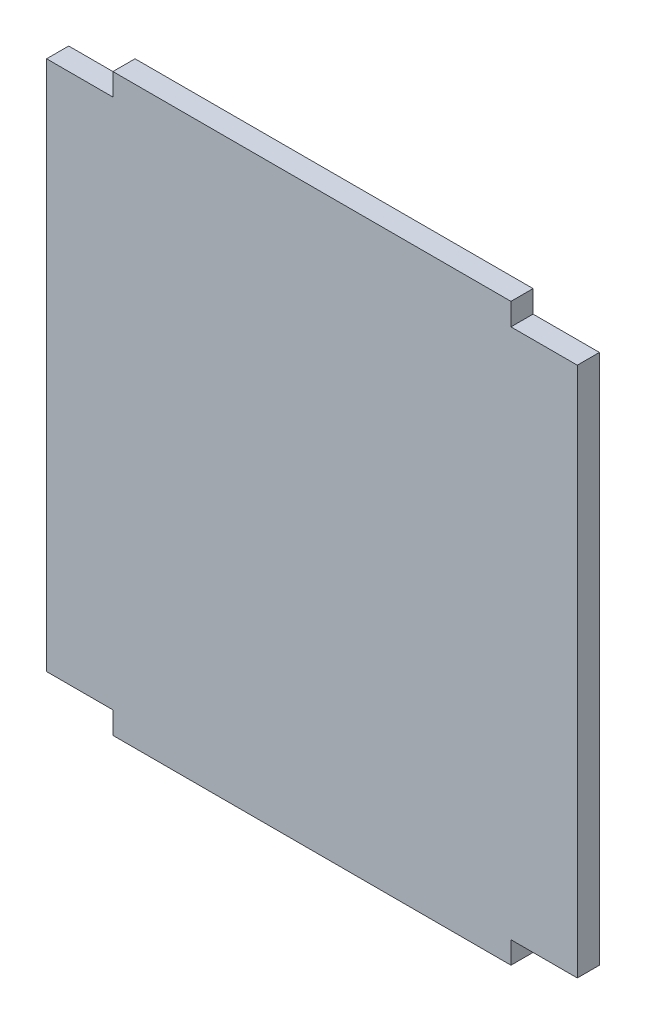
SolidWorks part; units mm, degrees
ref_plane "Front Plane" through (0, 0, 0) normal (0, 0, 1) x (1, 0, 0)
ref_plane "Top Plane" through (0, 0, 0) normal (0, 1, 0) x (1, 0, 0)
ref_plane "Right Plane" through (0, 0, 0) normal (1, 0, 0) x (0, 0, -1)
sketch "Sketch1" plane through (0, 0, 0) normal (0, 0, 1) x (1, 0, 0)
  line L1 (-38.1, -41.275) -> (38.1, -41.275)
  line L2 (-38.1, -41.275) -> (-38.1, 41.275)
  line L3 (-38.1, 41.275) -> (38.1, 41.275)
  line L4 (38.1, -41.275) -> (38.1, 41.275)
  line L5 (-38.1, -41.275) -> (38.1, 41.275) construction
  line L6 (-38.1, 41.275) -> (38.1, -41.275) construction
  point P0 (0, 0)
  dimension "D1" = 76.2
  dimension "D2" = 82.55
extrude "Boss-Extrude1" add sketch "Sketch1" along normal blind 3.175
sketch "Sketch2" plane through (0, 0, 0) normal (0, 0, -1) x (-1, 0, 0)
  line L0 (-38.1, 0) -> (38.1, 0) construction
  line L1 (-38.1, -41.275) -> (-28.575, -41.275)
  line L2 (-38.1, -41.275) -> (-38.1, -38.1)
  line L3 (-38.1, -38.1) -> (-28.575, -38.1)
  line L4 (-28.575, -41.275) -> (-28.575, -38.1)
  line L5 (38.1, -41.275) -> (28.575, -41.275)
  line L6 (38.1, -41.275) -> (38.1, -38.1)
  line L7 (38.1, -38.1) -> (28.575, -38.1)
  line L8 (28.575, -41.275) -> (28.575, -38.1)
  line L9 (-38.1, -41.275) -> (-38.1, 41.275) construction
  line L10 (38.1, 41.275) -> (38.1, -41.275) construction
  line L11 (28.575, 41.275) -> (28.575, 38.1)
  line L12 (38.1, 38.1) -> (28.575, 38.1)
  line L13 (38.1, 41.275) -> (38.1, 38.1)
  line L14 (38.1, 41.275) -> (28.575, 41.275)
  line L15 (-28.575, 41.275) -> (-28.575, 38.1)
  line L16 (-38.1, 38.1) -> (-28.575, 38.1)
  line L17 (-38.1, 41.275) -> (-38.1, 38.1)
  line L18 (-38.1, 41.275) -> (-28.575, 41.275)
  dimension "D1" = 3.175
  dimension "D2" = 57.15
extrude "Cut-Extrude1" cut sketch "Sketch2" against normal through all
